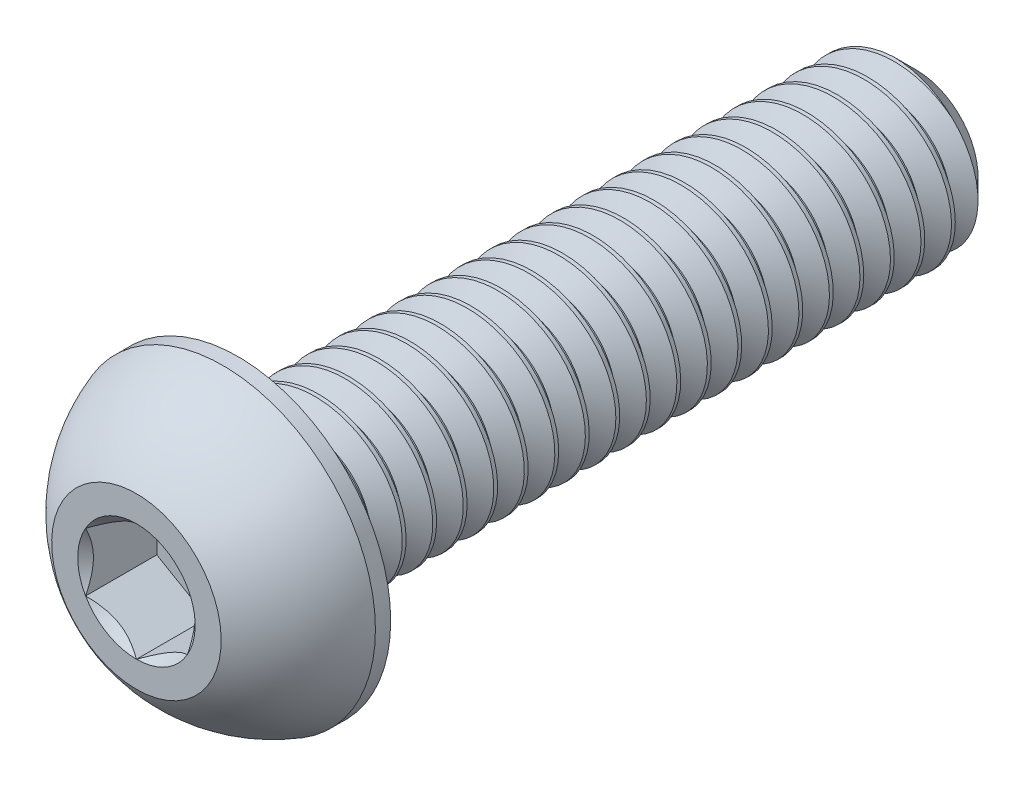
SolidWorks part; units mm, degrees
note: '?' marks a value the reader was unsure of.
ref_plane "Front" through (0, 0, 0) normal (0, 0, 1) x (1, 0, 0)
ref_plane "Top" through (0, 0, 0) normal (0, 1, 0) x (1, 0, 0)
ref_plane "Right" through (0, 0, 0) normal (1, 0, 0) x (0, 0, -1)
sketch "Sketch1" plane through (0, 0, 0) normal (1, 0, 0) x (0, 0, -1)
  line L2 (1.5, 1.25) -> (11.5, 1.25)
  line L3 (11.5, 1.25) -> (11.5, 0)
  line L4 (11.5, 0) -> (1.5, 0)
  line L6 (1.275, 2.25) -> (1.5, 2.25) construction
  line L7 (11.5, 1.25) -> (11.5, -1.25) construction
  line L8 (0, 0) -> (1.5, 0) construction
  line L9 (1.5, 2.25) -> (1.5, -2.25) construction
  line L11 (1.5, 1.25) -> (1.5, 0)
  line L13 (0, 0.75) -> (0, -0.75) construction
  line L14 (0, 0.75) -> (0, 1.25) construction
  arc A3 (0, 1.25) -> (1.275, 2.25) centre (2.01, 0) cw construction
  dimension "D1" = 0.225
  dimension "Head Ht" = 1.5
  dimension "Head Dia" = 4.5
  dimension "Dia" = 2.5
  dimension "Lg" = 10
  dimension "Hex" = 1.5
revolve "Revolve1" add sketch "Sketch1" angle 360 mid plane about L4
sketch "Sketch3" plane through (0, 0, -11.5) normal (0, 0, -1) x (-1, 0, 0)
  circle A0 centre (0, 0) radius 1.25
curve "Helix/Spiral1" pitch 0.45 height 10.45 turns 23.2222
chamfer "Chamfer1" distance 0.3375 angle 45 1 edges at (0, 1.25, -11.5)
sketch "Sketch7" plane through (0, 0, 0) normal (1, 0, 0) x (0, 0, -1)
  line L6 (1.275, 2.25) -> (1.5, 2.25) construction
  line L8 (0, 0) -> (1.5, 0) construction
  line L11 (1.5, 2.25) -> (1.5, -2.25) construction
  line L12 (1.275, 2.25) -> (1.5, 2.25)
  line L13 (0, 0) -> (1.5, 0)
  line L14 (0, 0.75) -> (0, -0.75) construction
  line L15 (1.5, 2.25) -> (1.5, 0)
  line L16 (0, 1.25) -> (0, 0)
  arc A2 (1.275, 2.25) -> (0, 1.25) centre (2.01, 0) ccw construction
  arc A3 (1.275, 2.25) -> (0, 1.25) centre (2.01, 0) ccw
revolve "Revolve2" add sketch "Sketch7" angle 360 mid plane about L13
sketch "Sketch5" plane through (0, 0, 0) normal (0, 0, 1) x (1, 0, 0)
  line L1 (0.75, -0.433) -> (0.75, 0.433)
  line L2 (0.75, 0.433) -> (0, 0.866)
  line L3 (0, 0.866) -> (-0.75, 0.433)
  line L4 (-0.75, 0.433) -> (-0.75, -0.433)
  line L5 (-0.75, -0.433) -> (0, -0.866)
  line L6 (0, -0.866) -> (0.75, -0.433)
  circle A0 centre (0, 0) radius 0.75 construction
extrude "Cut-Extrude2" cut sketch "Sketch5" against normal blind 1.05
sketch "Sketch6" plane through (0, 0, 0) normal (0, 0, 1) x (1, 0, 0)
  circle A0 centre (0, 0) radius 0.866
extrude "Cut-Extrude3" cut sketch "Sketch6" against normal blind 1.05 draft 45
sketch "Sketch2" plane through (0, 0, 0) normal (1, 0, 0) x (0, 0, -1)
  line L0 (11.1625, 1.25) -> (11.5562, 1.25)
  line L1 (11.5562, 1.25) -> (11.3875, 0.9577)
  line L2 (11.3875, 0.9577) -> (11.3312, 0.9577)
  line L3 (11.3312, 0.9577) -> (11.1625, 1.25)
  line L4 (11.2469, 1.1039) -> (11.4719, 1.1039) construction
  dimension "D1" = 60
  dimension "D2" = 0.0563
  dimension "D3" = 0.225
sweep "Cut-Sweep1" cut profiles "Sketch2" path "Helix/Spiral1"
sketch "Sketch10" plane through (0, 0, 0) normal (1, 0, 0) x (0, 0, -1)
  line L0 (11.5, 1.25) -> (11.5, -1.25) construction
  point P0 (10.825, -1.25)
  dimension "D1" = 0.675
ref_axis "Center Axis 1" through (0, 0, -8.1113) along (0, 0, 1)?
ref_plane "Contact Plane 1" through (0, 0, -1.5) normal (0, 0, -1) x (-1, 0, 0)
ref_plane "Contact Plane 2" through (0, 0, 0) normal (0, 0, 1) x (1, 0, 0)
equation "\"D3@Helix/Spiral1\" = \"Lg@Sketch1\" + \"D4@Helix/Spiral1\""
equation "\"D2@Sketch2\" = \"D4@Helix/Spiral1\" * .125"
equation "\"D3@Sketch2\" = \"D4@Helix/Spiral1\" * .5"
equation "\"D1@Chamfer1\" = \"D4@Helix/Spiral1\" * .75"
equation "\"D1@Cut-Extrude2\" = \"Head Ht@Sketch1\" * .7"
equation "\"D1@Sketch1\" = \"Head Ht@Sketch1\" * .15"
equation "\"D1@Sketch10\" = \"D4@Helix/Spiral1\" * 1.5"
equation "\"D1@Cut-Extrude3\" = \"D1@Cut-Extrude2\""
